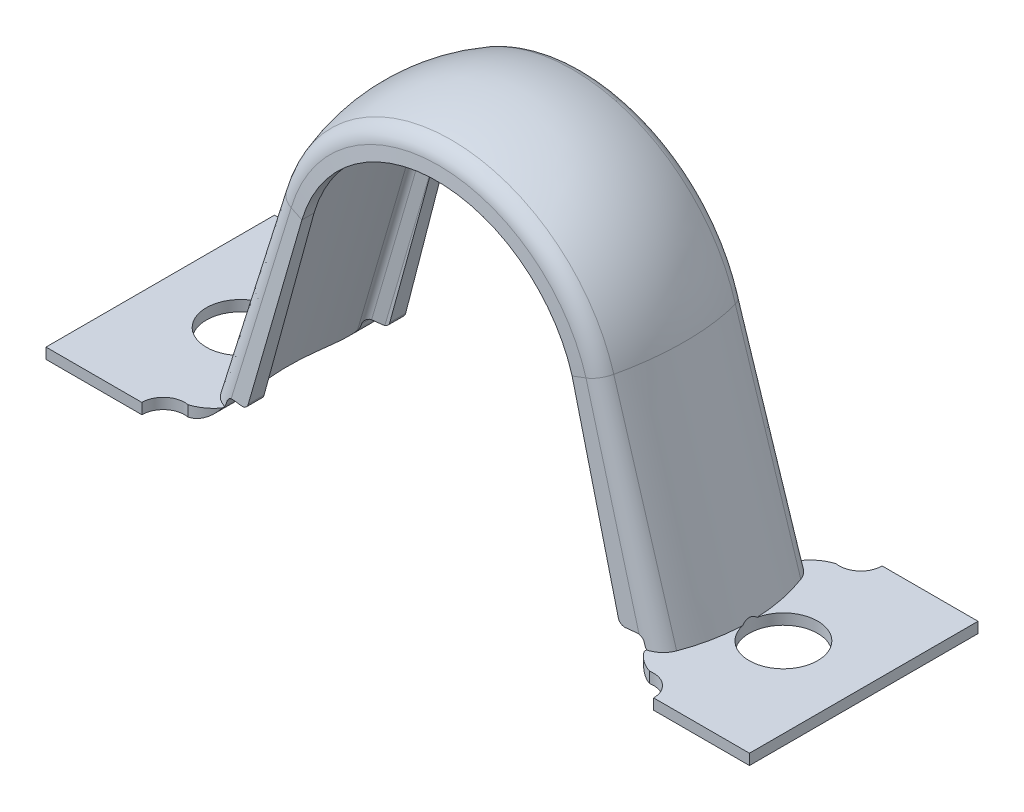
SolidWorks part; units mm, degrees
ref_plane "Alzado" through (0, 0, 0) normal (0, 0, 1) x (1, 0, 0)
ref_plane "Planta" through (0, 0, 0) normal (0, 1, 0) x (1, 0, 0)
ref_plane "Vista lateral" through (0, 0, 0) normal (1, 0, 0) x (0, 0, -1)
ref_plane "Plano1" through (0, 0, 0) normal (1, 0, 0) x (0, 0, -1)
sketch "Croquis1" plane through (0, 0, 0) normal (1, 0, 0) x (0, 0, -1)
  line L0 (-10.5, 19.7097) -> (-8.8, 19.7097)
  line L1 (-8.8, 19.7097) -> (-8.6064, 21.2939)
  line L2 (8.6064, 21.2939) -> (8.8, 19.7097)
  line L3 (8.8, 19.7097) -> (10.5, 19.7097)
  line L4 (10.5, 19.7097) -> (10.2806, 21.5049)
  line L5 (-10.2806, 21.5049) -> (-10.5, 19.7097)
  line L6 (16, 0) -> (-16, 0) construction
  arc A0 (-8.6064, 21.2939) -> (-7.9522, 22.1136) centre (-7.6138, 21.1726) cw
  arc A1 (-7.9522, 22.1136) -> (7.9522, 22.1136) centre (0, 0) cw
  arc A2 (7.9522, 22.1136) -> (8.6064, 21.2939) centre (7.6138, 21.1726) cw
  arc A3 (10.2806, 21.5049) -> (8.5126, 23.7187) centre (7.6006, 21.1774) ccw
  arc A4 (8.5126, 23.7187) -> (-8.5126, 23.7187) centre (0, 0) ccw
  arc A5 (-8.5126, 23.7187) -> (-10.2806, 21.5049) centre (-7.6006, 21.1774) ccw
revolve "Revolución1" add sketch "Croquis1" angle 360 about L6 reverse direction yes
ref_plane "Plano2" through (0, 0, 0) normal (0, 0, 1) x (1, 0, 0)
sketch "Croquis2" plane through (0, 0, 0) normal (0, 0, 1) x (1, 0, 0)
  line L0 (-49.25, -23.8) -> (-49.25, -25.3)
  line L1 (-49.25, -25.3) -> (-32.1261, -25.3)
  line L2 (-27.8068, -22.0625) -> (-25.6206, -14.5834)
  line L3 (25.6206, -14.5834) -> (27.8068, -22.0625)
  line L4 (32.1261, -25.3) -> (49.25, -25.3)
  line L5 (49.25, -25.3) -> (49.25, -23.8)
  line L6 (49.25, -23.8) -> (32.1261, -23.8)
  line L7 (29.2465, -21.6417) -> (28.4159, -18.8)
  line L8 (28.4159, -18.8) -> (47.61, -13.1894)
  line L9 (47.61, -13.1894) -> (40.3105, 11.783)
  line L10 (40.3105, 11.783) -> (0, 0)
  line L11 (0, 0) -> (-40.3105, 11.783)
  line L12 (-40.3105, 11.783) -> (-47.61, -13.1894)
  line L13 (-47.61, -13.1894) -> (-28.4159, -18.8)
  line L14 (-28.4159, -18.8) -> (-29.2465, -21.6417)
  line L15 (-32.1261, -23.8) -> (-49.25, -23.8)
  arc A0 (-32.1261, -25.3) -> (-27.8068, -22.0625) centre (-32.1261, -20.8) ccw
  arc A1 (-25.6206, -14.5834) -> (-21.1328, -13.9102) centre (-23.221, -15.2848) cw
  arc A2 (-21.1328, -13.9102) -> (21.1328, -13.9102) centre (0, 0) ccw
  arc A3 (21.1328, -13.9102) -> (25.6206, -14.5834) centre (23.221, -15.2848) cw
  arc A4 (27.8068, -22.0625) -> (32.1261, -25.3) centre (32.1261, -20.8) ccw
  arc A5 (32.1261, -23.8) -> (29.2465, -21.6417) centre (32.1261, -20.8) cw
  arc A6 (-29.2465, -21.6417) -> (-32.1261, -23.8) centre (-32.1261, -20.8) cw
extrude "Cortar-Extruir1" cut sketch "Croquis2" against normal blind 16 and the other way blind 16
ref_plane "Plano3" through (0, 0, 0) normal (0.2806, 0.9598, 0) x (0.9598, -0.2806, 0)
sketch "Croquis3" plane through (0, 0, 0) normal (0.2806, 0.9598, 0) x (0.9598, -0.2806, 0)
  line L0 (-21.5049, -10.2806) -> (-19.7097, -10.5)
  line L1 (-19.7097, -10.5) -> (-19.7097, -8.8)
  line L2 (-19.7097, -8.8) -> (-21.2939, -8.6064)
  line L3 (-21.2939, 8.6064) -> (-19.7097, 8.8)
  line L4 (-19.7097, 8.8) -> (-19.7097, 10.5)
  line L5 (-19.7097, 10.5) -> (-21.5049, 10.2806)
  line L6 (0, 16) -> (0, -16) construction
  arc A0 (-23.7187, 8.5126) -> (-23.7187, -8.5126) centre (0, 0) ccw
  arc A1 (-23.7187, -8.5126) -> (-21.5049, -10.2806) centre (-21.1774, -7.6006) ccw
  arc A2 (-21.2939, -8.6064) -> (-22.1136, -7.9522) centre (-21.1726, -7.6138) cw
  arc A3 (-22.1136, -7.9522) -> (-22.1136, 7.9522) centre (0, 0) cw
  arc A4 (-22.1136, 7.9522) -> (-21.2939, 8.6064) centre (-21.1726, 7.6138) cw
  arc A5 (-21.5049, 10.2806) -> (-23.7187, 8.5126) centre (-21.1774, 7.6006) ccw
extrude "Saliente-Extruir1" add sketch "Croquis3" against normal blind 34 draft 1 draft outward yes
ref_plane "Plano4" through (0, 0, 0) normal (-0.2806, 0.9598, 0) x (0.9598, 0.2806, 0)
sketch "Croquis4" plane through (0, 0, 0) normal (-0.2806, 0.9598, 0) x (0.9598, 0.2806, 0)
  line L0 (19.7097, -8.8) -> (19.7097, -10.5)
  line L1 (19.7097, -10.5) -> (21.5049, -10.2806)
  line L2 (21.5049, 10.2806) -> (19.7097, 10.5)
  line L3 (19.7097, 10.5) -> (19.7097, 8.8)
  line L4 (19.7097, 8.8) -> (21.2939, 8.6064)
  line L5 (21.2939, -8.6064) -> (19.7097, -8.8)
  line L6 (0, -16) -> (0, 16) construction
  arc A0 (21.5049, -10.2806) -> (23.7187, -8.5126) centre (21.1774, -7.6006) ccw
  arc A1 (23.7187, -8.5126) -> (23.7187, 8.5126) centre (0, 0) ccw
  arc A2 (23.7187, 8.5126) -> (21.5049, 10.2806) centre (21.1774, 7.6006) ccw
  arc A3 (21.2939, 8.6064) -> (22.1136, 7.9522) centre (21.1726, 7.6138) cw
  arc A4 (22.1136, 7.9522) -> (22.1136, -7.9522) centre (0, 0) cw
  arc A5 (22.1136, -7.9522) -> (21.2939, -8.6064) centre (21.1726, -7.6138) cw
extrude "Saliente-Extruir2" add sketch "Croquis4" against normal blind 34 draft 1 draft outward yes
ref_plane "Plano5" through (0, 0, 0) normal (0, 0, 1) x (1, 0, 0)
sketch "Croquis5" plane through (0, 0, 0) normal (0, 0, 1) x (1, 0, 0)
  line L0 (-49.25, -23.8) -> (-9.25, -23.8)
  line L1 (-9.25, -23.8) -> (-9.25, -22.3)
  line L2 (-9.25, -22.3) -> (-49.25, -22.3)
  line L3 (-49.25, -22.3) -> (-49.25, -23.8)
extrude "Saliente-Extruir3" add sketch "Croquis5" against normal blind 16 and the other way blind 16
ref_plane "Plano6" through (0, 0, 0) normal (0, 0, 1) x (1, 0, 0)
sketch "Croquis6" plane through (0, 0, 0) normal (0, 0, 1) x (1, 0, 0)
  line L0 (9.25, -23.8) -> (49.25, -23.8)
  line L1 (49.25, -23.8) -> (49.25, -22.3)
  line L2 (49.25, -22.3) -> (9.25, -22.3)
  line L3 (9.25, -22.3) -> (9.25, -23.8)
extrude "Saliente-Extruir4" add sketch "Croquis6" against normal blind 16 and the other way blind 16
ref_plane "Plano7" through (0, 0, 0) normal (0, 1, 0) x (1, 0, 0)
sketch "Croquis7" plane through (0, 0, 0) normal (0, 1, 0) x (1, 0, 0)
  circle A0 centre (-38, 0) radius 4.8
extrude "Cortar-Extruir2" cut sketch "Croquis7" against normal blind 49.25
ref_plane "Plano8" through (0, 0, 0) normal (0, 1, 0) x (1, 0, 0)
sketch "Croquis8" plane through (0, 0, 0) normal (0, 1, 0) x (1, 0, 0)
  circle A0 centre (38, 0) radius 4.8
extrude "Cortar-Extruir3" cut sketch "Croquis8" against normal blind 36
ref_plane "Plano9" through (0, 0, 0) normal (-0.2806, 0.9598, 0) x (0.9598, 0.2806, 0)
sketch "Croquis9" plane through (0, 0, 0) normal (-0.2806, 0.9598, 0) x (0.9598, 0.2806, 0)
  line L0 (14.7097, 8.8) -> (14.7097, -8.8)
  line L1 (14.7097, -8.8) -> (19.7097, -8.8)
  line L2 (19.7097, -8.8) -> (21.2939, -8.6064)
  line L3 (21.2939, 8.6064) -> (19.7097, 8.8)
  line L4 (19.7097, 8.8) -> (14.7097, 8.8)
  line L5 (0, -16) -> (0, 16) construction
  arc A0 (21.2939, -8.6064) -> (22.1136, -7.9522) centre (21.1726, -7.6138) ccw
  arc A1 (22.1136, -7.9522) -> (22.1136, 7.9522) centre (0, 0) ccw
  arc A2 (22.1136, 7.9522) -> (21.2939, 8.6064) centre (21.1726, 7.6138) ccw
extrude "Cortar-Extruir4" cut sketch "Croquis9" against normal blind 46
ref_plane "Plano10" through (0, 0, 0) normal (0.2806, 0.9598, 0) x (0.9598, -0.2806, 0)
sketch "Croquis10" plane through (0, 0, 0) normal (0.2806, 0.9598, 0) x (0.9598, -0.2806, 0)
  line L0 (-21.2939, -8.6064) -> (-19.7097, -8.8)
  line L1 (-19.7097, -8.8) -> (-14.7097, -8.8)
  line L2 (-14.7097, -8.8) -> (-14.7097, 8.8)
  line L3 (-14.7097, 8.8) -> (-19.7097, 8.8)
  line L4 (-19.7097, 8.8) -> (-21.2939, 8.6064)
  line L5 (0, 16) -> (0, -16) construction
  arc A0 (-22.1136, 7.9522) -> (-22.1136, -7.9522) centre (0, 0) ccw
  arc A1 (-22.1136, -7.9522) -> (-21.2939, -8.6064) centre (-21.1726, -7.6138) ccw
  arc A2 (-21.2939, 8.6064) -> (-22.1136, 7.9522) centre (-21.1726, 7.6138) ccw
extrude "Cortar-Extruir5" cut sketch "Croquis10" against normal blind 46
ref_plane "Plano11" through (0, -23.8, 0) normal (0, 1, 0) x (1, 0, 0)
sketch "Croquis11" plane through (0, -23.8, 0) normal (0, 1, 0) x (1, 0, 0)
  line L0 (-35.8333, -16) -> (-28.4655, -16)
  line L1 (-28.4655, -16) -> (-28.4655, -7.7949)
  arc A0 (-28.4655, -7.7949) -> (-32.3227, -13.0438) centre (-33.9655, -7.7949) cw
  arc A1 (-32.3227, -13.0438) -> (-35.8333, -16) centre (-32.8333, -16) ccw
extrude "Cortar-Extruir6" cut sketch "Croquis11" against normal blind 1.5 and the other way blind 1.5
ref_plane "Plano12" through (0, -23.8, 0) normal (0, 1, 0) x (1, 0, 0)
sketch "Croquis12" plane through (0, -23.8, 0) normal (0, 1, 0) x (1, 0, 0)
  line L0 (-28.4655, 7.7949) -> (-28.4655, 16)
  line L1 (-28.4655, 16) -> (-35.8333, 16)
  arc A0 (-35.8333, 16) -> (-32.3227, 13.0438) centre (-32.8333, 16) ccw
  arc A1 (-32.3227, 13.0438) -> (-28.4655, 7.7949) centre (-33.9655, 7.7949) cw
extrude "Cortar-Extruir7" cut sketch "Croquis12" along normal blind 1.5
ref_plane "Plano13" through (0, -23.8, 0) normal (0, 1, 0) x (1, 0, 0)
sketch "Croquis13" plane through (0, -23.8, 0) normal (0, 1, 0) x (1, 0, 0)
  line L0 (35.8333, 16) -> (28.4655, 16)
  line L1 (28.4655, 16) -> (28.4655, 7.7949)
  arc A0 (28.4655, 7.7949) -> (32.3227, 13.0438) centre (33.9655, 7.7949) cw
  arc A1 (32.3227, 13.0438) -> (35.8333, 16) centre (32.8333, 16) ccw
extrude "Cortar-Extruir8" cut sketch "Croquis13" along normal blind 1.5
ref_plane "Plano14" through (0, -23.8, 0) normal (0, 1, 0) x (1, 0, 0)
sketch "Croquis14" plane through (0, -23.8, 0) normal (0, 1, 0) x (1, 0, 0)
  line L0 (28.4655, -7.7949) -> (28.4655, -16)
  line L1 (28.4655, -16) -> (35.8333, -16)
  arc A0 (35.8333, -16) -> (32.3227, -13.0438) centre (32.8333, -16) ccw
  arc A1 (32.3227, -13.0438) -> (28.4655, -7.7949) centre (33.9655, -7.7949) cw
extrude "Cortar-Extruir9" cut sketch "Croquis14" against normal blind 1.5 and the other way blind 1.5
ref_plane "Plano15" through (0, 0, 0) normal (0, 0, 1) x (1, 0, 0)
sketch "Croquis15" plane through (0, 0, 0) normal (0, 0, 1) x (1, 0, 0)
  line L0 (-49.25, -32.3) -> (-0.6261, -32.3)
  line L1 (-0.6261, -32.3) -> (-0.6261, -20.8)
  line L2 (-0.6261, -20.8) -> (-28.2531, -20.8)
  line L3 (-32.1261, -23.8) -> (-49.25, -23.8)
  line L4 (-49.25, -23.8) -> (-49.25, -32.3)
  arc A0 (-28.2531, -20.8) -> (-29.2213, -21.55) centre (-28.2531, -21.8) ccw
  arc A1 (-29.2213, -21.55) -> (-32.1261, -23.8) centre (-32.1261, -20.8) cw
extrude "Cortar-Extruir10" cut sketch "Croquis15" against normal blind 34 and the other way blind 34
ref_plane "Plano16" through (0, 0, 0) normal (0, 0, 1) x (1, 0, 0)
sketch "Croquis16" plane through (0, 0, 0) normal (0, 0, 1) x (1, 0, 0)
  line L0 (0.6261, -32.3) -> (49.25, -32.3)
  line L1 (49.25, -32.3) -> (49.25, -23.8)
  line L2 (49.25, -23.8) -> (32.1261, -23.8)
  line L3 (28.2531, -20.8) -> (0.6261, -20.8)
  line L4 (0.6261, -20.8) -> (0.6261, -32.3)
  arc A0 (32.1261, -23.8) -> (29.2213, -21.55) centre (32.1261, -20.8) cw
  arc A1 (29.2213, -21.55) -> (28.2531, -20.8) centre (28.2531, -21.8) ccw
extrude "Cortar-Extruir11" cut sketch "Croquis16" against normal blind 26 and the other way blind 26
fillet "Redondeo1" radius 1 4 edges at (26.1181, -20.8, -9.9191) (-26.1181, -20.8, 9.9191) (26.1181, -20.8, 9.9191) (-26.1181, -20.8, -9.9191)
